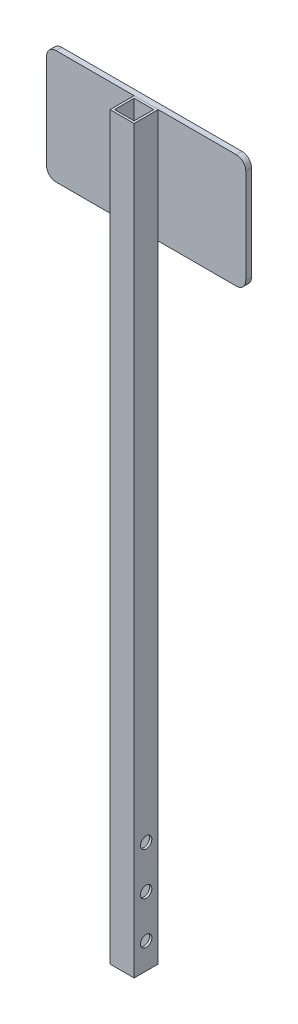
SolidWorks part; units mm, degrees
ref_plane "Front Plane" through (0, 0, 0) normal (0, 0, 1) x (1, 0, 0)
ref_plane "Top Plane" through (0, 0, 0) normal (0, 1, 0) x (1, 0, 0)
ref_plane "Right Plane" through (0, 0, 0) normal (1, 0, 0) x (0, 0, -1)
sketch "Sketch1" plane through (0, 0, 0) normal (1, 0, 0) x (0, 0, -1)
  line L1 (-6.35, 0) -> (6.35, 0)
  line L2 (-6.35, 0) -> (-6.35, -390)
  line L3 (-6.35, -390) -> (6.35, -390)
  line L4 (6.35, 0) -> (6.35, -390)
  circle A0 centre (0, -376.25) radius 3
  circle A2 centre (0, -353.75) radius 3
  circle A3 centre (0, -331.25) radius 3
  point P10 (0, -390)
  point P11 (0, 0)
  dimension "D3" = 13.75
  dimension "D4" = 6
  dimension "D1" = 12.7
  dimension "D2" = 390
  dimension "D5" = 3
extrude "Boss-Extrude1" add sketch "Sketch1" along normal mid plane 12.7 contours L4 L1 L2 L3 A3 A2 A0 | A2 | A3 | A0 region at (0, -192.2339, 0) region at (0, -376.25, 0) region at (0, -353.75, 0) region at (0, -331.25, 0)
shell "Shell1" thickness 1.2 removed face at (0, 0, 0) removed face at (0, -390, 0)
extrude "Cut-Extrude1" cut sketch "Sketch1<3>" against normal through all both and the other way through all contours A0 | A2 | A3
sketch "Sketch1<3>" plane through (0, 0, 0) normal (1, 0, 0) x (0, 0, -1) same geometry as "Sketch1"
sketch "Sketch2" plane through (0, 0, -6.35) normal (0, 0, -1) x (-1, 0, 0)
  line L1 (-47.5, -60) -> (47.5, -60)
  line L2 (-52.5, -55) -> (-52.5, -5)
  line L3 (-47.5, 0) -> (47.5, 0)
  line L4 (52.5, -55) -> (52.5, -5)
  arc A0 (-47.5, -60) -> (-52.5, -55) centre (-47.5, -55) cw
  arc A1 (47.5, -60) -> (52.5, -55) centre (47.5, -55) ccw
  arc A2 (47.5, 0) -> (52.5, -5) centre (47.5, -5) cw
  arc A3 (-52.5, -5) -> (-47.5, 0) centre (-47.5, -5) cw
  point P11 (52.5, 0)
  point P14 (-52.5, 0)
  dimension "D3" = 5
  dimension "D1" = 105
  dimension "D2" = 60
extrude "Boss-Extrude2" add sketch "Sketch2" along normal blind 3 separate body
